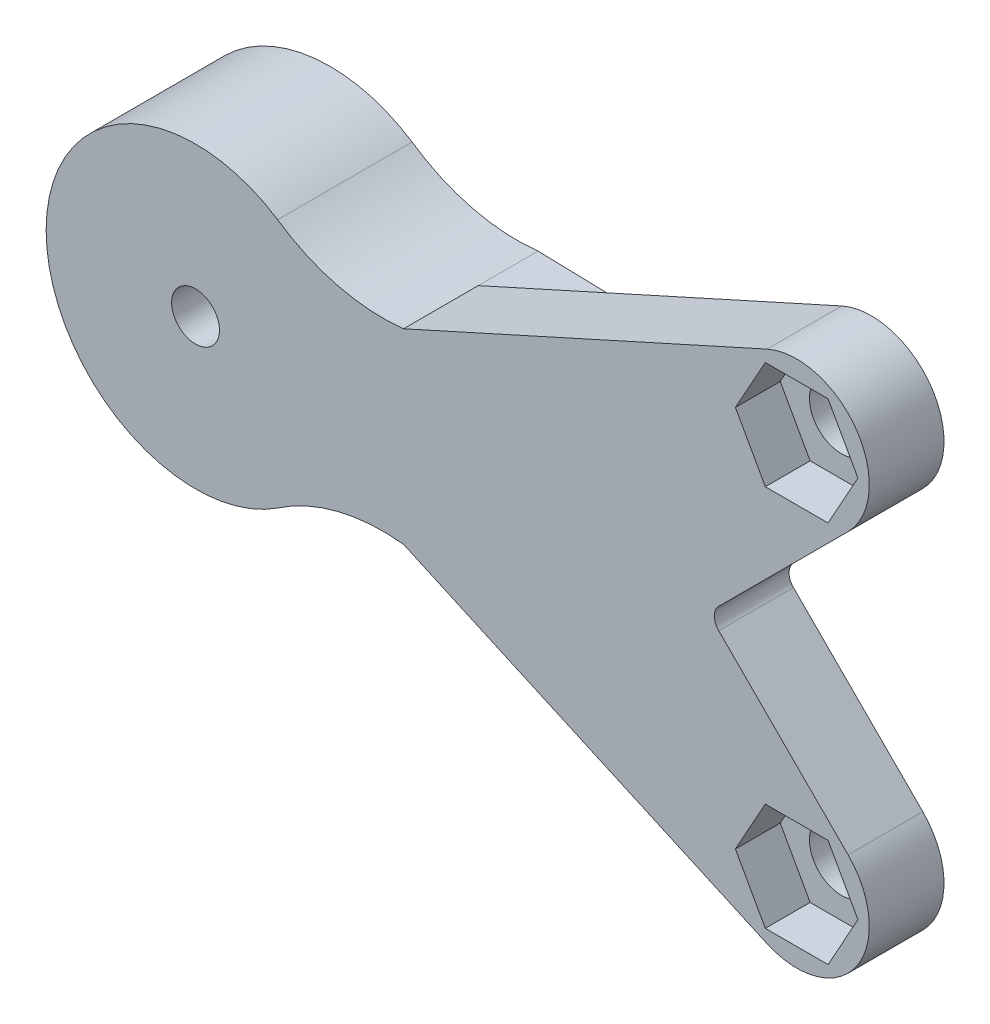
SolidWorks part; units mm, degrees
ref_plane "Front Plane" through (0, 0, 0) normal (0, 0, 1) x (1, 0, 0)
ref_plane "Top Plane" through (0, 0, 0) normal (0, 1, 0) x (1, 0, 0)
ref_plane "Right Plane" through (0, 0, 0) normal (1, 0, 0) x (0, 0, -1)
sketch "Sketch1" plane through (0, 0, 0) normal (0, 0, 1) x (1, 0, 0)
  line L0 (0, 0) -> (30, 0) construction
  line L1 (23.9358, 6.0642) -> (13.9235, 6.25)
  line L2 (23.9358, -6.0642) -> (13.9235, -6.25)
  circle A0 centre (0, 0) radius 10.25
  circle A1 centre (0, 0) radius 7.75
  circle A2 centre (23.9358, 0) radius 6.0642
  arc A3 (13.9235, -6.25) -> (5.8141, -8.4415) centre (13.9834, -22.5716) ccw
  arc A4 (13.9235, 6.25) -> (5.8141, 8.4415) centre (13.9834, 22.5716) cw
  dimension "D1" = 30
sketch "Sketch2" plane through (0, 0, 0) normal (0, 0, 1) x (1, 0, 0)
  line L0 (23.9358, 6) -> (13.9235, 6.25)
  line L1 (6.1485, 0) -> (17.0076, 0) construction
  line L2 (0, 0) -> (30, 0) construction
  line L3 (23.9358, -6) -> (13.9235, -6.25)
  circle A0 centre (0, 0) radius 10
  circle A1 centre (23.9358, 0) radius 6
  arc A2 (13.9235, 6.25) -> (5.4936, 8.3559) centre (12.5319, 18.6049) cw
  arc A3 (13.9235, -6.25) -> (5.4936, -8.3559) centre (12.5319, -18.6049) ccw
  dimension "D1" = 20
  dimension "D2" = 12
extrude "Boss-Extrude1" add sketch "Sketch2" along normal blind 9 contours A3 A0 A2 | A3 L3 A1 L0 A2 A0 | A1 A3 region at (14.1767, 0, 0) region at (23.9358, 0, 0) region at (0, 0, 0)
sketch "Sketch5" plane through (0, 0, 9) normal (0, 0, 1) x (1, 0, 0)
  line L0 (0.1412, 0.2013) -> (17.8157, 0.2013) construction
  line L1 (24.077, 6.4626) -> (14.1672, 6.4513)
  line L2 (43.6739, 9.3663) -> (34.5376, 0.2013)
  line L3 (14.1672, 6.4513) -> (38.2461, 17.2328)
  line L4 (30.3383, 0.2013) -> (49.9499, 0.2013) construction
  line L5 (24.077, -6.06) -> (14.1672, -6.0487)
  line L6 (14.1672, -6.0487) -> (38.2461, -16.8301)
  line L7 (43.6739, -8.9637) -> (34.5376, 0.2013)
  circle A0 centre (40.2321, 12.7973) radius 2.1427
  circle A1 centre (40.2321, -12.3947) radius 2.1427
  circle A2 centre (40.2321, 12.7973) radius 4.8598
  circle A3 centre (40.2321, -12.3947) radius 4.8598
  arc A4 (24.077, -6.06) -> (24.077, 6.4626) centre (24.077, 0.2013) ccw
  circle A5 centre (40.2321, -12.3947) radius 2.1427
  circle A6 centre (40.2321, -12.3947) radius 4.8598
sketch "Sketch6" plane through (0, 0, 9) normal (0, 0, 1) x (1, 0, 0)
  line L0 (13.9235, 6.25) -> (38.2461, 17.2328)
  line L1 (43.6739, -9.3663) -> (34.3075, 0)
  line L2 (29.9358, 0) -> (37.4938, 0) construction
  line L3 (43.6739, 9.3663) -> (34.3075, 0)
  line L4 (13.9235, 6.25) -> (23.9358, 6)
  line L6 (23.9358, 6) -> (23.9879, 0) construction
  line L7 (13.9235, -6.25) -> (38.2461, -17.2328)
  line L8 (13.9235, -6.25) -> (23.9358, -6)
  circle A1 centre (40.2321, 12.7973) radius 4.8598
  circle A2 centre (40.2321, 12.7973) radius 2.1427
  arc A3 (23.9363, -5.9476) -> (23.9363, 5.9476) centre (23.9879, 0) ccw
  circle A4 centre (40.2321, -12.7973) radius 2.1427
  circle A5 centre (40.2321, -12.7973) radius 4.8598
  line M9 (13.9235, -6.25) -> (23.9358, -6)
  arc M10 (23.9358, -6) -> (23.9358, 6) centre (23.9358, 0) ccw
  line M11 (23.9358, 6) -> (13.9235, 6.25)
extrude "Boss-Extrude2" add sketch "Sketch6" against normal blind 5 contours L7 A5 L1 L3 A1 L0 M11 M10 M9 | A5 L7 A4 | L0 A1 A2 region at (33.008, 0, 9)
sketch "Sketch7" plane through (0, 0, 0) normal (0, 0, -1) x (-1, 0, 0)
  line L0 (5.5826, 0.0309) -> (19.9826, 0.0309) construction
  line L1 (17.8815, 2.4988) -> (8.4018, 4.0309)
  line L2 (8.4018, 4.0309) -> (3.9018, 4.0309)
  line L3 (17.8815, -2.4371) -> (8.4018, -3.9691)
  line L4 (8.4018, -3.9691) -> (3.9018, -3.9691)
  line L5 (-0.0174, 5.6309) -> (-0.0174, -5.5691) construction
  line L6 (-8.4365, -3.9691) -> (-3.9365, -3.9691)
  line L7 (-17.9162, -2.4371) -> (-8.4365, -3.9691)
  line L8 (-17.9162, 2.4988) -> (-8.4365, 4.0309)
  line L9 (-8.4365, 4.0309) -> (-3.9365, 4.0309)
  circle A0 centre (-0.0174, 0.0309) radius 5.6
  arc A1 (17.8815, 2.4988) -> (17.8815, -2.4371) centre (17.4826, 0.0309) cw
  arc A2 (-17.9162, 2.4988) -> (-17.9162, -2.4371) centre (-17.5174, 0.0309) ccw
extrude "Cut-Extrude1" cut sketch "Sketch7" against normal blind 6 contours L8 A2 L7 L6 A0 L9 | A0 | A1 L1 L3 | A0 L4 L3 L1 L2 region at (-11.5646, 0.0309, 0) region at (0.0174, 0.0309, 0) region at (11.5993, 0.0309, 0)
sketch "Sketch9" plane through (0, 0, 6) normal (0, 0, -1) x (-1, 0, 0)
  circle A0 centre (0, 0) radius 1.6
  dimension "D1" = 3.2
extrude "Cut-Extrude2" cut sketch "Sketch9" against normal blind 6
sketch "Sketch10" plane through (0, 0, 9) normal (0, 0, 1) x (1, 0, 0)
  line L0 (34.3075, 0) -> (29.817, 0) construction
  line L1 (38.1321, 9.1973) -> (42.3321, 9.1973)
  line L3 (38.1321, 16.3973) -> (42.3321, 16.3973)
  line L5 (38.1321, -9.1973) -> (36.1321, -12.7973)
  line L6 (36.1321, -12.7973) -> (38.1321, -16.3973)
  line L7 (36.1321, 12.7973) -> (38.1321, 16.3973)
  line L8 (38.1321, 9.1973) -> (36.1321, 12.7973)
  line L9 (38.1321, -16.3973) -> (42.3321, -16.3973)
  line L10 (42.3321, 9.1973) -> (44.3321, 12.7973)
  line L11 (44.3321, 12.7973) -> (42.3321, 16.3973)
  line L12 (44.3321, -12.7973) -> (42.3321, -16.3973)
  line L13 (42.3321, -9.1973) -> (44.3321, -12.7973)
  line L14 (38.1321, -9.1973) -> (42.3321, -9.1973)
  point P0 (40.2321, 12.7973)
  dimension "D1" = 7.2
  dimension "D2" = 4.2
extrude "Cut-Extrude3" cut sketch "Sketch10" against normal blind 3
fillet "Fillet1" radius 1 1 edges at (34.3075, 0, 6.5)
